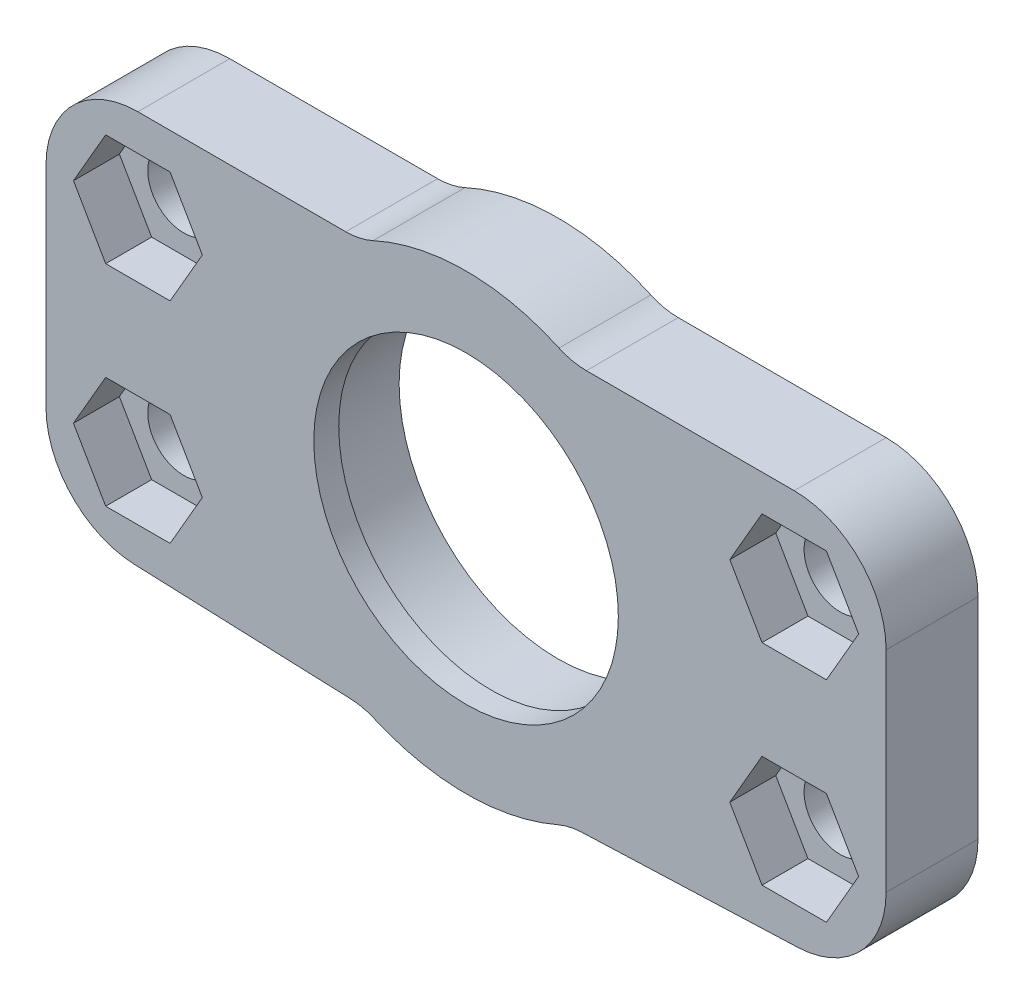
SolidWorks part; units mm, degrees
ref_plane "Front Plane" through (0, 0, 0) normal (0, 0, 1) x (1, 0, 0)
ref_plane "Top Plane" through (0, 0, 0) normal (0, 1, 0) x (1, 0, 0)
ref_plane "Right Plane" through (0, 0, 0) normal (1, 0, 0) x (0, 0, -1)
sketch "Sketch1" plane through (0, 0, 0) normal (0, 0, 1) x (1, 0, 0)
  line L0 (-8, 15) -> (-25, 15)
  line L1 (-32, 8) -> (-32, -8)
  line L2 (-25, 8) -> (-25, -8) construction
  line L3 (-7.7992, -15.666) -> (-25.2687, -14.9948)
  line L5 (0, 17) -> (0, 11.6)
  line L6 (0, -11.6) -> (0, -17.5)
  arc A0 (0, 11.6) -> (0, -11.6) centre (0, 0) ccw
  arc A1 (0, 17) -> (-8, 15) centre (0, 0) ccw
  arc A2 (-7.7992, -15.666) -> (0, -17.5) centre (0, 0) ccw
  circle A3 centre (-25, 8) radius 2.75
  arc A4 (-25, 15) -> (-32, 8) centre (-25, 8) ccw
  circle A5 centre (-25, -8) radius 2.75
  arc A6 (-32, -8) -> (-25.2687, -14.9948) centre (-25, -8) ccw
  dimension "D2" = 11.6
  dimension "D3" = 17
  dimension "D4" = 17.5
  dimension "D5" = 7
  dimension "D6" = 5.5
  dimension "D1" = 16
  dimension "D7" = 25
  dimension "D8" = 8
  dimension "D9" = 92.2
extrude "Boss-Extrude1" add sketch "Sketch1" along normal mid plane 7 separate body
sketch "Sketch2" plane through (0, 0, -3.5) normal (0, 0, -1) x (-1, 0, 0)
  circle A0 centre (0, 0) radius 12.1
  dimension "D1" = 24.2
extrude "Cut-Extrude1" cut sketch "Sketch2" against normal blind 5.1
sketch "Sketch3" plane through (0, 0, 3.5) normal (0, 0, 1) x (1, 0, 0)
  line L1 (-27.4537, 12.25) -> (-29.9075, 8)
  line L2 (-29.9075, 8) -> (-27.4537, 3.75)
  line L3 (-27.4537, 3.75) -> (-22.5463, 3.75)
  line L4 (-22.5463, 3.75) -> (-20.0925, 8)
  line L5 (-20.0925, 8) -> (-22.5463, 12.25)
  line L6 (-22.5463, 12.25) -> (-27.4537, 12.25)
  line L7 (-27.4537, -3.75) -> (-29.9075, -8)
  line L8 (-29.9075, -8) -> (-27.4537, -12.25)
  line L9 (-27.4537, -12.25) -> (-22.5463, -12.25)
  line L10 (-22.5463, -12.25) -> (-20.0925, -8)
  line L11 (-20.0925, -8) -> (-22.5463, -3.75)
  line L12 (-22.5463, -3.75) -> (-27.4537, -3.75)
  circle A0 centre (-25, 8) radius 4.25 construction
  circle A1 centre (-25, -8) radius 4.25 construction
  dimension "D1" = 8.5
extrude "Cut-Extrude2" cut sketch "Sketch3" against normal blind 3.5
fillet "Fillet1" radius 5 2 edges at (-7.7992, -15.666, 0) (-8, 15, 0)
mirror "Mirror1" about plane through (0, 17, 3.5) normal (-1, 0, 0) of bodies 104
